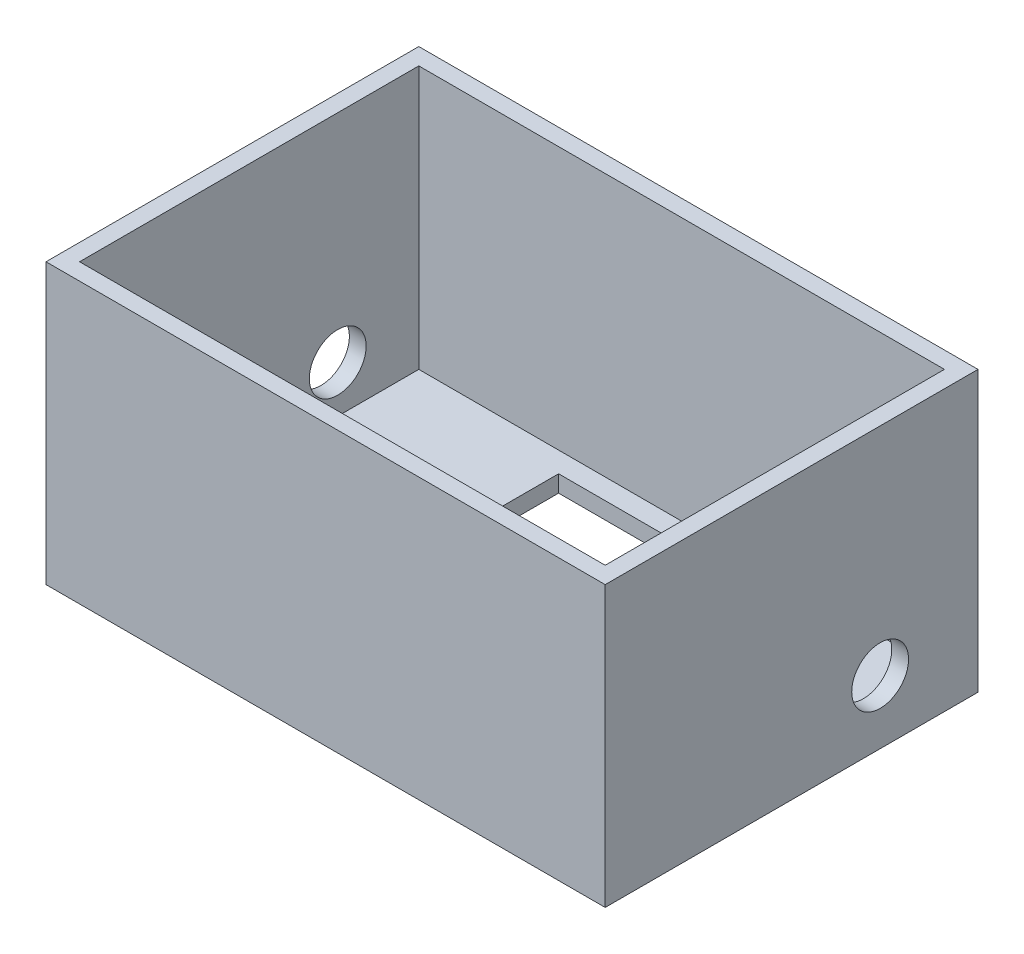
SolidWorks part; units mm, degrees
ref_plane "Front Plane" through (0, 0, 0) normal (0, 0, 1) x (1, 0, 0)
ref_plane "Top Plane" through (0, 0, 0) normal (0, 1, 0) x (1, 0, 0)
ref_plane "Right Plane" through (0, 0, 0) normal (1, 0, 0) x (0, 0, -1)
sketch "Sketch2" plane through (0, 0, 0) normal (0, 1, 0) x (1, 0, 0)
  line L1 (0, 0) -> (60, 0)
  line L2 (0, 0) -> (0, 40)
  line L3 (0, 40) -> (60, 40)
  line L4 (60, 0) -> (60, 40)
  line L5 (41, 23) -> (19, 23)
  line L6 (41, 23) -> (41, 36)
  line L7 (41, 36) -> (19, 36)
  line L8 (19, 23) -> (19, 36)
  line L9 (41, 23) -> (19, 36) construction
  line L10 (41, 36) -> (19, 23) construction
  point P5 (30, 29.5)
  point P10 (0, 0)
  point P11 (0, 0)
  point P12 (41.0232, 37.5902)
  point P13 (0, 0)
  point P14 (0, 0)
  point P15 (0, 0)
  point P16 (0, 0)
  dimension "D1" = 60
  dimension "D2" = 40
  dimension "D3" = 13
  dimension "D4" = 22
  dimension "D5" = 19
  dimension "D6" = 4
extrude "Boss-Extrude1" add sketch "Sketch2" along normal blind 30 contours L2 L1 L4 L3
shell "Shell2" thickness 1.8 removed face at (30, 30, -20)
extrude "Cut-Extrude4" cut sketch "Sketch2<6>" along normal blind 30 contours L8 L5 L6 L7 region at (30, 0, -29.5)
sketch "Sketch2<6>" plane through (0, 0, 0) normal (0, 1, 0) x (1, 0, 0) same geometry as "Sketch2"
hole_wizard "Ø6.0mm Dowel Hole1" positions "Sketch3" profile "Sketch4" hole size "Ø6.0" standard "ANSI Metric" end condition through all
sketch "Sketch3" plane through (0, 0, 0) normal (-1, 0, 0) x (0, 0, 1)
  line L0 (0, 0) -> (-40, 0) construction
  line L1 (-40, 30) -> (-40, 0) construction
  point P0 (-29.5, 6.8)
  dimension "D1" = 6.8
  dimension "D2" = 10.5
sketch "Sketch4" plane through (0, 6.8, -29.5) normal (0, 1, 0) x (0, 0, 1)
  line L0 (0, 0) -> (0, 60)
  line L1 (0, 60) -> (3.05, 60)
  line L2 (3.05, 60) -> (3.05, 0)
  line L5 (3.05, 0) -> (0, 0)
  line L11 (0, -6.35) -> (0, 107.95) construction
  dimension "Thru Hole Dia." = 6.1
  dimension "Thru Hole Depth" = 60
